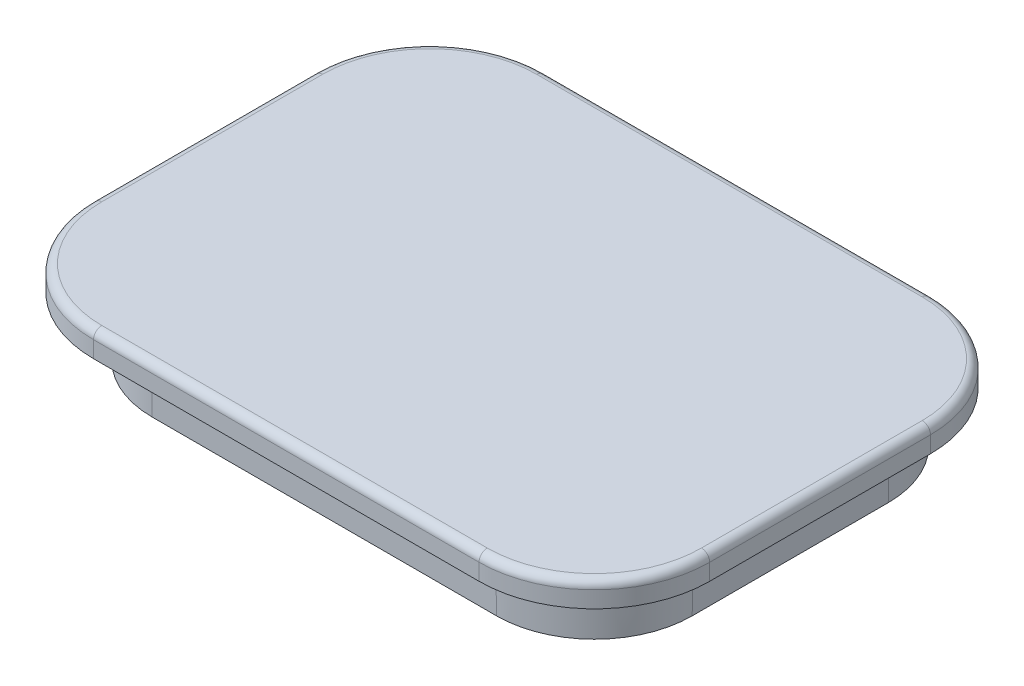
SolidWorks part; units mm, degrees
ref_plane "Front" through (0, 0, 0) normal (0, 0, 1) x (1, 0, 0)
ref_plane "Top" through (0, 0, 0) normal (0, 1, 0) x (1, 0, 0)
ref_plane "Right" through (0, 0, 0) normal (1, 0, 0) x (0, 0, -1)
sketch "Sketch1" plane through (0, 0, 0) normal (0, 1, 0) x (1, 0, 0)
  line L1 (6, 0) -> (26.9, 0)
  line L2 (0, 6) -> (0, 17.9)
  line L3 (6, 23.9) -> (26.9, 23.9)
  line L4 (32.9, 6) -> (32.9, 17.9)
  arc A0 (6, 0) -> (0, 6) centre (6, 6) cw
  arc A1 (26.9, 0) -> (32.9, 6) centre (26.9, 6) ccw
  arc A2 (26.9, 23.9) -> (32.9, 17.9) centre (26.9, 17.9) cw
  arc A3 (0, 17.9) -> (6, 23.9) centre (6, 17.9) cw
  point P7 (0, 0)
  point P10 (32.9, 0)
  point P13 (32.9, 23.9)
  point P16 (0, 23.9)
  dimension "D3" = 6
  dimension "D1" = 32.9
  dimension "D2" = 23.9
extrude "Boss-Extrude1" add sketch "Sketch1" along normal blind 3.6
sketch "Sketch2" plane through (0, 3.6, 0) normal (0, 1, 0) x (1, 0, 0)
  line L0 (0, 17.9) -> (0, 6) construction
  line L1 (4.75, 25.15) -> (28.15, 25.15)
  line L2 (-2.25, 18.15) -> (-2.25, 4.75)
  line L3 (4.75, -2.25) -> (28.15, -2.25)
  line L4 (35.15, 18.15) -> (35.15, 4.75)
  line L5 (26.9, 23.9) -> (6, 23.9) construction
  line L6 (32.9, 6) -> (32.9, 17.9) construction
  line L7 (6, 0) -> (26.9, 0) construction
  arc A0 (-2.25, 4.75) -> (4.75, -2.25) centre (4.75, 4.75) ccw
  arc A1 (28.15, -2.25) -> (35.15, 4.75) centre (28.15, 4.75) ccw
  arc A2 (28.15, 25.15) -> (35.15, 18.15) centre (28.15, 18.15) cw
  arc A3 (4.75, 25.15) -> (-2.25, 18.15) centre (4.75, 18.15) ccw
  dimension "D5" = 7
  dimension "D1" = 2.25
  dimension "D2" = 1.25
  dimension "D3" = 2.25
  dimension "D4" = 2.25
extrude "Boss-Extrude2" add sketch "Sketch2" along normal blind 1.5
sketch "Sketch3" plane through (0, 0, 0) normal (0, -1, 0) x (1, 0, 0)
  line L0 (26.9, -23.9) -> (6, -23.9) construction
  line L1 (25.7, -22.7) -> (7.2, -22.7)
  line L2 (31.7, -16.7) -> (31.7, -7.2)
  line L3 (25.7, -1.2) -> (7.2, -1.2)
  line L4 (1.2, -16.7) -> (1.2, -7.2)
  line L5 (32.9, -6) -> (32.9, -17.9) construction
  line L6 (6, 0) -> (26.9, 0) construction
  line L7 (0, -17.9) -> (0, -6) construction
  arc A0 (7.2, -22.7) -> (1.2, -16.7) centre (7.2, -16.7) cw
  arc A1 (7.2, -1.2) -> (1.2, -7.2) centre (7.2, -7.2) ccw
  arc A2 (31.7, -7.2) -> (25.7, -1.2) centre (25.7, -7.2) ccw
  arc A3 (25.7, -22.7) -> (31.7, -16.7) centre (25.7, -16.7) ccw
  dimension "D5" = 6
  dimension "D1" = 1.2
  dimension "D2" = 1.2
  dimension "D3" = 1.2
  dimension "D4" = 1.2
extrude "Cut-Extrude1" cut sketch "Sketch3" against normal blind 3.6
sketch "Sketch5" plane through (0, 3.6, 0) normal (0, -1, 0) x (1, 0, 0)
  line L0 (7.2, -22.7) -> (25.7, -22.7) construction
  line L1 (7.2, -1.2) -> (8.4, -1.2)
  line L2 (7.2, -1.2) -> (7.2, -6.2)
  line L3 (7.2, -22.7) -> (8.4, -22.7)
  line L4 (8.4, -1.2) -> (8.4, -6.2)
  line L5 (1.2, -7.2) -> (1.2, -16.7) construction
  line L6 (25.7, -1.2) -> (24.5, -1.2)
  line L7 (25.7, -1.2) -> (25.7, -6.2)
  line L8 (25.7, -22.7) -> (24.5, -22.7)
  line L9 (24.5, -1.2) -> (24.5, -6.2)
  line L10 (31.7, -16.7) -> (26.7, -16.7)
  line L11 (31.7, -16.7) -> (31.7, -15.5)
  line L12 (31.7, -15.5) -> (26.7, -15.5)
  line L13 (1.2, -16.7) -> (1.2, -15.5)
  line L14 (31.7, -16.7) -> (31.7, -7.2) construction
  line L15 (1.2, -7.2) -> (6.2, -7.2)
  line L16 (1.2, -7.2) -> (1.2, -8.4)
  line L17 (1.2, -8.4) -> (6.2, -8.4)
  line L18 (31.7, -7.2) -> (31.7, -8.4)
  line L19 (9.4, -7.2) -> (23.5, -7.2)
  line L20 (7.2, -9.4) -> (7.2, -14.5)
  line L21 (9.4, -8.4) -> (23.5, -8.4)
  line L22 (8.4, -9.4) -> (8.4, -14.5)
  line L23 (24.5, -9.4) -> (24.5, -14.5)
  line L24 (25.7, -9.4) -> (25.7, -14.5)
  line L25 (26.7, -7.2) -> (31.7, -7.2)
  line L26 (26.7, -8.4) -> (31.7, -8.4)
  line L27 (23.5, -15.5) -> (9.4, -15.5)
  line L28 (23.5, -16.7) -> (9.4, -16.7)
  line L29 (24.5, -17.7) -> (24.5, -22.7)
  line L30 (25.7, -17.7) -> (25.7, -22.7)
  line L31 (7.2, -17.7) -> (7.2, -22.7)
  line L32 (6.2, -15.5) -> (1.2, -15.5)
  line L33 (8.4, -17.7) -> (8.4, -22.7)
  line L34 (6.2, -16.7) -> (1.2, -16.7)
  arc A0 (23.5, -16.7) -> (24.5, -17.7) centre (23.5, -17.7) cw
  arc A1 (26.7, -16.7) -> (25.7, -17.7) centre (26.7, -17.7) ccw
  arc A2 (26.7, -15.5) -> (25.7, -14.5) centre (26.7, -14.5) cw
  arc A3 (23.5, -15.5) -> (24.5, -14.5) centre (23.5, -14.5) ccw
  arc A4 (25.7, -6.2) -> (26.7, -7.2) centre (26.7, -6.2) ccw
  arc A5 (25.7, -9.4) -> (26.7, -8.4) centre (26.7, -9.4) cw
  arc A6 (24.5, -9.4) -> (23.5, -8.4) centre (23.5, -9.4) ccw
  arc A7 (24.5, -6.2) -> (23.5, -7.2) centre (23.5, -6.2) cw
  arc A8 (9.4, -15.5) -> (8.4, -14.5) centre (9.4, -14.5) cw
  arc A9 (8.4, -17.7) -> (9.4, -16.7) centre (9.4, -17.7) cw
  arc A10 (7.2, -17.7) -> (6.2, -16.7) centre (6.2, -17.7) ccw
  arc A11 (7.2, -14.5) -> (6.2, -15.5) centre (6.2, -14.5) cw
  arc A12 (7.2, -9.4) -> (6.2, -8.4) centre (6.2, -9.4) ccw
  arc A13 (9.4, -8.4) -> (8.4, -9.4) centre (9.4, -9.4) ccw
  arc A14 (9.4, -7.2) -> (8.4, -6.2) centre (9.4, -6.2) cw
  arc A15 (6.2, -7.2) -> (7.2, -6.2) centre (6.2, -6.2) ccw
  point P44 (24.5, -16.7)
  point P47 (25.7, -16.7)
  point P54 (25.7, -7.2)
  point P57 (25.7, -8.4)
  point P68 (7.2, -16.7)
  point P71 (7.2, -15.5)
  point P76 (8.4, -8.4)
  dimension "D5" = 1
  dimension "D1" = 1.2
  dimension "D2" = 1.2
  dimension "D3" = 1.2
  dimension "D4" = 1.2
extrude "Boss-Extrude5" add sketch "Sketch5" along normal blind 3.6
chamfer "Chamfer1" distance 3.6 angle 1 8 edges at (0, 0, -11.95) (1.7574, 0, -1.7574) (1.7574, 0, -22.1426) (16.45, 0, 0) (16.45, 0, -23.9) (31.1426, 0, -1.7574) (31.1426, 0, -22.1426) (32.9, 0, -11.95) first distance on face at (0, 1.8, -11.95) first distance on face at (2.3787, 1.8, -2.3787) first distance on face at (2.3787, 1.8, -21.5213) first distance on face at (16.45, 1.8, 0) first distance on face at (16.45, 1.8, -23.9) first distance on face at (30.5213, 1.8, -2.3787) first distance on face at (30.5213, 1.8, -21.5213) first distance on face at (32.9, 1.8, -11.95)
fillet "Fillet3" radius 1 16 edges at (1.2, 1.8, -16.7) (1.2, 1.8, -8.4) (31.7, 1.8, -8.4) (24.5, 1.8, -1.2) (24.5, 1.8, -22.7) (25.7, 1.8, -1.2) (8.4, 1.8, -1.2) (7.2, 1.8, -1.2) (31.7, 1.8, -16.7) (31.7, 1.8, -7.2) (31.7, 1.8, -15.5) (7.2, 1.8, -22.7) (1.2, 1.8, -7.2) (1.2, 1.8, -15.5) (8.4, 1.8, -22.7) (25.7, 1.8, -22.7)
fillet "Fillet4" radius 0.5 8 edges at (-0.1997, 5.1, 0.1997) (-2.25, 5.1, -11.45) (-0.1997, 5.1, -23.0997) (16.45, 5.1, -25.15) (33.0997, 5.1, -23.0997) (35.15, 5.1, -11.45) (33.0997, 5.1, 0.1997) (16.45, 5.1, 2.25)
